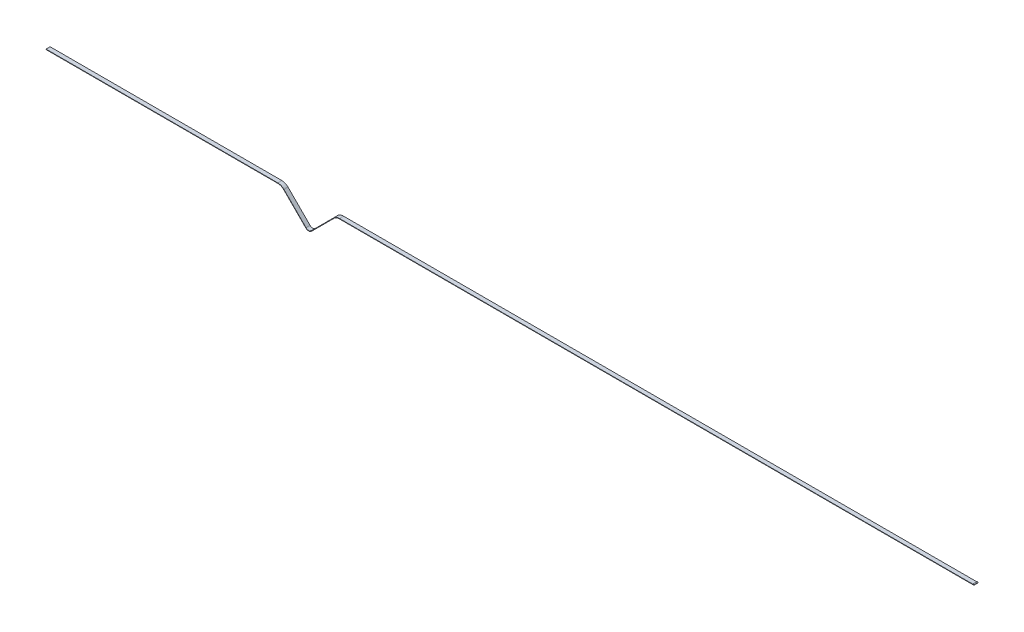
SolidWorks part; units mm, degrees
ref_plane "Front Plane" through (0, 0, 0) normal (0, 0, 1) x (1, 0, 0)
ref_plane "Top Plane" through (0, 0, 0) normal (0, 1, 0) x (1, 0, 0)
ref_plane "Right Plane" through (0, 0, 0) normal (1, 0, 0) x (0, 0, -1)
sketch "Sketch1" plane through (0, 0, 0) normal (1, 0, 0) x (0, 0, -1)
  line L1 (0, 0) -> (6, 0)
  line L2 (0, 0) -> (0, 0.63)
  line L3 (0, 0.63) -> (6, 0.63)
  line L4 (6, 0) -> (6, 0.63)
  dimension "D1" = 0.63
  dimension "D2" = 6
sketch "Sketch2" plane through (0, 0, 0) normal (0, 0, 1) x (1, 0, 0)
  line L0 (0, 0) -> (-937.7651, 0)
  line L1 (-946.2202, -3.5053) -> (-979.012, -36.3377)
  line L2 (-987.6582, -36.3377) -> (-1020.4499, -3.5053)
  line L3 (-1028.9051, 0) -> (-1371.6, 0)
  arc A0 (-937.7651, 0) -> (-946.2202, -3.5053) centre (-937.7651, -11.95) ccw
  arc A1 (-979.012, -36.3377) -> (-987.6582, -36.3377) centre (-983.3351, -32.02) cw
  arc A2 (-1020.4499, -3.5053) -> (-1028.9051, 0) centre (-1028.9051, -11.95) ccw
  circle A4 centre (-983.3351, -32.02) radius 6.11 construction
  circle A6 centre (-937.7651, -11.95) radius 11.95 construction
  circle A7 centre (-1028.9051, -11.95) radius 11.95 construction
  dimension "D1" = 6.11
  dimension "D4" = 1371.6
sweep "Sweep1" add profiles "Sketch1" path "Sketch2"
sketch "Sketch3" plane through (0, 0, 0) normal (0, 0, 1) x (1, 0, 0)
  line L0 (0, 0.63) -> (-937.7651, 0.63) construction
  line L1 (-1.5, 0.63) -> (-1.5, 0)
  line L2 (0, 0) -> (-937.7651, 0) construction
  line L3 (-1.5, 0) -> (0, 0)
  line L4 (0, 0) -> (0, 0.63)
  arc A1 (0, 0.63) -> (-1.5, 0.63) centre (-0.75, 0.63) ccw
  dimension "D1" = 0.75
extrude "Boss-Extrude1" add sketch "Sketch3" against normal through all
pattern_curve "CrvPattern1" [suppressed] of bodies 102 driven by "Sketch2" parameters "D1"=2000, "D3"=2, "D2"=1, "D4"=10
